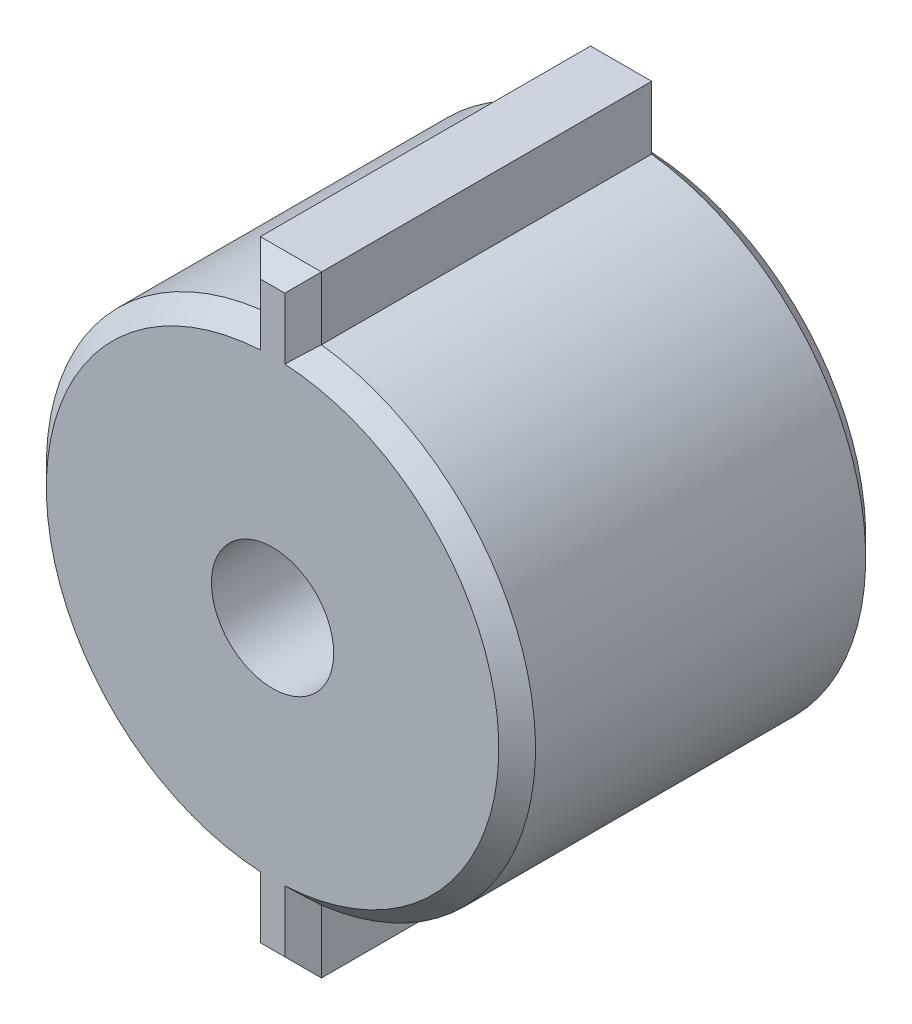
SolidWorks part; units mm, degrees
ref_plane "Ebene vorne" through (0, 0, 0) normal (0, 0, 1) x (1, 0, 0)
ref_plane "Ebene oben" through (0, 0, 0) normal (0, 1, 0) x (1, 0, 0)
ref_plane "Ebene rechts" through (0, 0, 0) normal (1, 0, 0) x (0, 0, -1)
sketch "Sketch1" plane through (0, 0, 0) normal (0, 0, 1) x (1, 0, 0)
  line L1 (0.25, -2.5) -> (-0.25, -2.5)
  line L2 (0.25, -2.5) -> (0.25, 2.5)
  line L3 (0.25, 2.5) -> (-0.25, 2.5)
  line L4 (-0.25, -2.5) -> (-0.25, 2.5)
  line L5 (0.25, -2.5) -> (-0.25, 2.5) construction
  line L6 (0.25, 2.5) -> (-0.25, -2.5) construction
  circle A0 centre (0, 0) radius 2
  circle A1 centre (0, 0) radius 0.5
  dimension "D1" = 4
  dimension "D4" = 1
  dimension "D2" = 0.5
  dimension "D3" = 5
extrude "Boss-Extrude1" add sketch "Sketch1" along normal mid plane 3 contours A1 L2 A0 L4 | A0 L2 L3 L4 | A1 L2 A0 | A1 L4 A0 L2 | A1 L4 A0 | A0 L4 L1 L2 region at (0, -2.2474, 0) region at (0, -1.2364, 0) region at (1.0044, 0, 0) region at (-1.0044, 0, 0) region at (0, 1.2364, 0) region at (0, 2.2474, 0)
chamfer "Chamfer1" distance 0.15 angle 45 16 edges at (-0.25, -2.2422, -1.5) (0, -2.5, -1.5) (0.25, -2.2422, -1.5) (2, 0, -1.5) (0.25, 2.2422, -1.5) (0, 2.5, -1.5) (-0.25, 2.2422, -1.5) (-2, 0, -1.5) (-0.25, 2.2422, 1.5) (0, 2.5, 1.5) (0.25, 2.2422, 1.5) (2, 0, 1.5) (0.25, -2.2422, 1.5) (0, -2.5, 1.5) (-0.25, -2.2422, 1.5) (-2, 0, 1.5)
